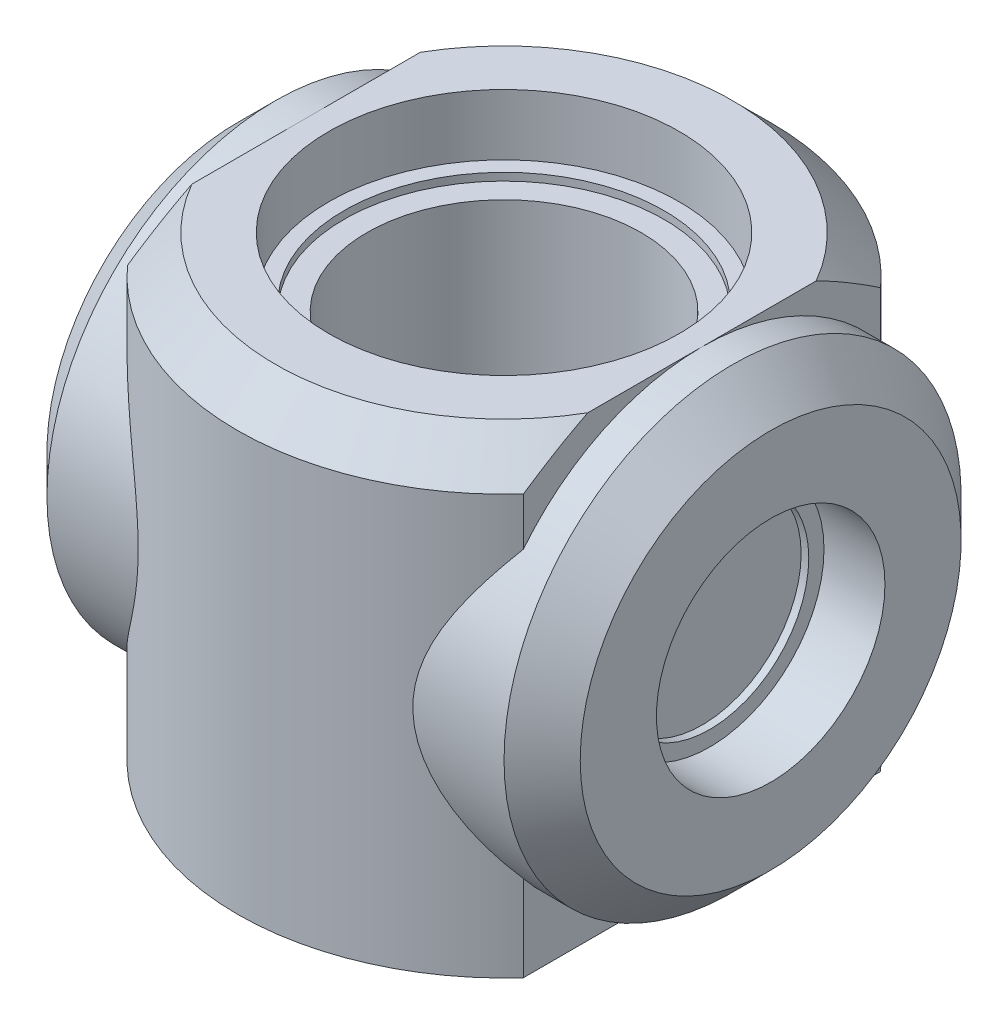
SolidWorks part; units mm, degrees
ref_plane "Front Plane" through (0, 0, 0) normal (0, 0, 1) x (1, 0, 0)
ref_plane "Top Plane" through (0, 0, 0) normal (0, 1, 0) x (1, 0, 0)
ref_plane "Right Plane" through (0, 0, 0) normal (1, 0, 0) x (0, 0, -1)
sketch "Sketch3" plane through (0, 0, 0) normal (0, 1, 0) x (1, 0, 0)
  line L0 (0, 0) -> (-13, 0) construction
  line L1 (-13, 0) -> (-13, 6.5)
  line L2 (-13.5, 7.5) -> (-17.5, 7.5)
  line L3 (-17.5, 7.5) -> (-17.5, 15)
  line L4 (-17.5, 15) -> (0, 15)
  line L5 (0, 15) -> (0, 0)
  line L6 (-13.5, 7.5) -> (-13.5, 6.5)
  line L7 (-13.5, 6.5) -> (-13, 6.5)
  line L8 (0, 0) -> (-13, 0)
  line L9 (-13, 0) -> (-23.8412, 0) construction
  dimension "D1" = 4.5
  dimension "D2" = 0.5
  dimension "D3" = 1
  dimension "D4" = 15
  dimension "D5" = 17.5
  dimension "D6" = 30
revolve "Revolve1" add sketch "Sketch3" angle 360 about L0 region at (-7.8029, 0, -8.051)
mirror "Mirror1" about plane through (0, 0, 0) normal (1, 0, 0) of "Revolve1"
sketch "Sketch6" plane through (0, 0, 0) normal (0, 1, 0) x (1, 0, 0)
  line L0 (-12.9936, 11.7225) -> (-12.9936, -11.7225)
  line L1 (12.9936, 11.7225) -> (12.9936, -11.7225)
  line L2 (-17.4936, 0.4737) -> (-17.4936, 3.9653) construction
  circle A0 centre (0, 0) radius 17.5
  dimension "D1" = 4.5
  dimension "D2" = 35
extrude "Boss-Extrude1" add sketch "Sketch6" against normal mid plane 30 contours L1 A0 L0 region at (0, 0, 0)
sketch "Sketch8" plane through (0, 0, 0) normal (0, 0, 1) x (1, 0, 0)
  line L0 (0, 0) -> (0, -16.9734) construction
  line L1 (0, -15) -> (11.5, -15)
  line L2 (-12.9936, -15) -> (12.9936, -15) construction
  line L3 (11.5, -15) -> (11.5, -11)
  line L4 (11.5, -11) -> (10.5, -11)
  line L5 (10.5, -11) -> (10.5, -10.5)
  line L6 (10.5, -10.5) -> (9, -10.5)
  line L7 (9, -10.5) -> (9, 10.5)
  line L9 (0, 0) -> (9, 0) construction
  line L10 (0, 15) -> (11.5, 15)
  line L11 (11.5, 15) -> (11.5, 11)
  line L12 (11.5, 11) -> (10.5, 11)
  line L13 (10.5, 11) -> (10.5, 10.5)
  line L14 (10.5, 10.5) -> (9, 10.5)
  line L15 (0, 15) -> (0, -15)
  dimension "D1" = 23
  dimension "D2" = 4
  dimension "D3" = 21
  dimension "D4" = 0.5
  dimension "D5" = 18
revolve "Cut-Revolve1" cut sketch "Sketch8" angle 360 about L15
chamfer "Chamfer1" distance 2.5 angle 45 4 edges at (17.5, 0, -15) (-17.5, 0, -15) (0, 15, -17.5) (0, 15, 17.5)
